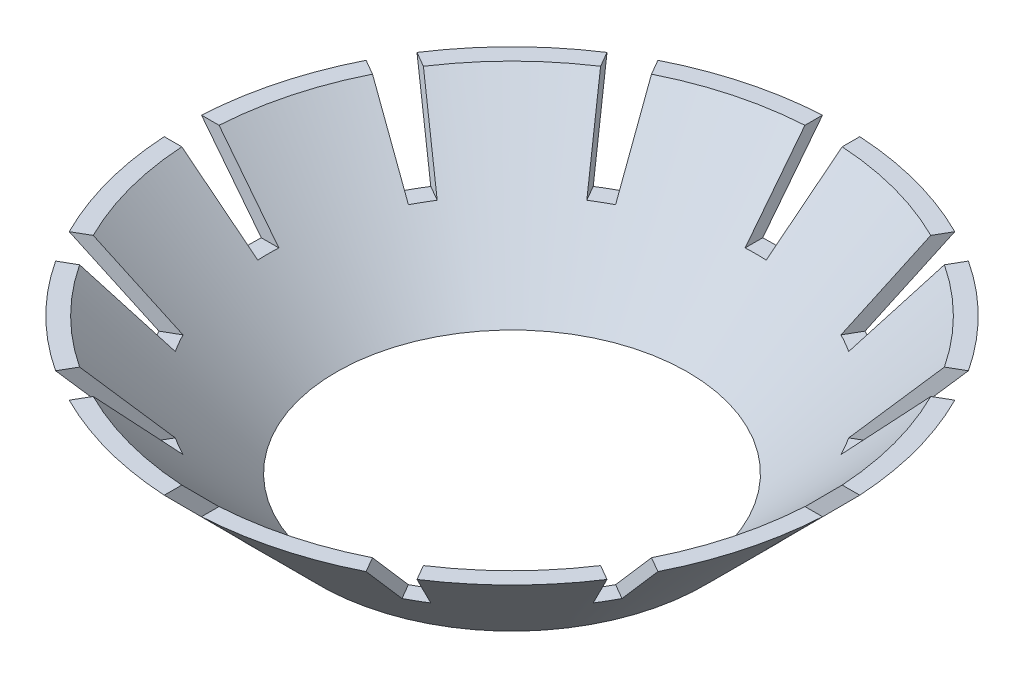
SolidWorks part; units mm, degrees
ref_plane "Plane1" through (0, 0, 0) normal (0, 0, 1) x (1, 0, 0)
ref_plane "Plane2" through (0, 0, 0) normal (0, 1, 0) x (1, 0, 0)
ref_plane "Plane3" through (0, 0, 0) normal (1, 0, 0) x (0, 0, -1)
sketch "Sketch1" plane through (0, 0, 0) normal (1, 0, 0) x (0, 0, -1)
  line L0 (0, -30) -> (0, 30) construction
  line L1 (8.5, 0) -> (15.1, 6.6)
  line L2 (8.5, 0) -> (9.3485, 0)
  line L3 (9.3485, 0) -> (15.9485, 6.6)
  line L4 (15.1, 6.6) -> (15.9485, 6.6)
  dimension "D1" = 45
  dimension "Thickness" = 0.6
revolve "Base-Revolve" add sketch "Sketch1" angle 360 about L0
sketch "Sketch2" plane through (0, 0, 0) normal (0, 0, 1) x (1, 0, 0)
  line L0 (0, 3.3) -> (0, 7.6) construction
  line L1 (-0.51, 3.3) -> (0.51, 3.3)
  line L2 (0, -30) -> (0, 30) construction
  line L3 (-1.02, 7.6) -> (1.02, 7.6)
  line L4 (-0.51, 3.3) -> (-1.02, 7.6)
  line L5 (0.51, 3.3) -> (1.02, 7.6)
  dimension "D1" = 3.3
  dimension "D2" = 1.02
  dimension "D3" = 4.3
  dimension "D4" = 2.04
extrude "Cut-Extrude1" cut sketch "Sketch2" against normal through all
pattern_circular "CirPattern1" count 12 over 360 about axis through (0, -30, 0) along (0, 1, 0) of "Cut-Extrude1"
equation "\"D1@Sketch2\" =  ( \"OutsideDia@Sketch1\" - \"InsideDia@Sketch1\" )  / 4"
equation "\"D2@Sketch2\" = \"InsideDia@Sketch1\" * .06"
equation "\"D4@Sketch2\" = \"D2@Sketch2\" * 2"
equation "\"D3@Sketch2\" = \"D1@Sketch2\" + 1"
